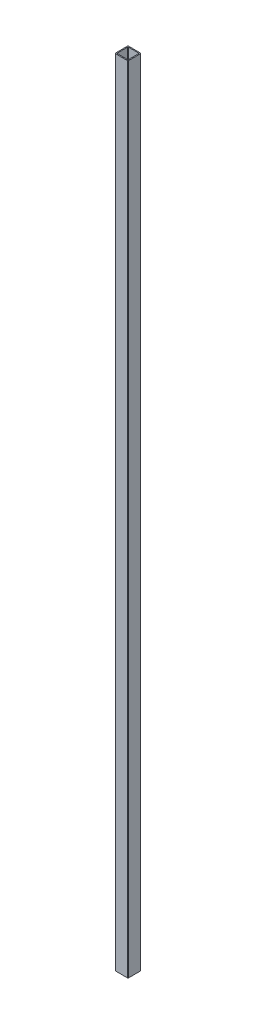
SolidWorks part; units mm, degrees
material "Hexcel AS4C (3000 Filaments)"
ref_plane "Front Plane" through (0, 0, 0) normal (0, 0, 1) x (1, 0, 0)
ref_plane "Top Plane" through (0, 0, 0) normal (0, 1, 0) x (1, 0, 0)
ref_plane "Right Plane" through (0, 0, 0) normal (1, 0, 0) x (0, 0, -1)
sketch "Sketch1" plane through (0, 0, 0) normal (0, 1, 0) x (1, 0, 0)
  line L1 (-9, -10) -> (9, -10)
  line L2 (-10, -9) -> (-10, 9)
  line L3 (-9, 10) -> (9, 10)
  line L4 (10, -9) -> (10, 9)
  line L5 (-10, -10) -> (10, 10) construction
  line L6 (-10, 10) -> (10, -10) construction
  line L7 (-7.5, -8.5) -> (7.5, -8.5)
  line L8 (-8.5, -7.5) -> (-8.5, 7.5)
  line L9 (-7.5, 8.5) -> (7.5, 8.5)
  line L10 (8.5, -7.5) -> (8.5, 7.5)
  line L11 (-8.5, -8.5) -> (8.5, 8.5) construction
  line L12 (-8.5, 8.5) -> (8.5, -8.5) construction
  arc A0 (-9, -10) -> (-10, -9) centre (-9, -9) cw
  arc A1 (9, 10) -> (10, 9) centre (9, 9) cw
  arc A2 (9, -10) -> (10, -9) centre (9, -9) ccw
  arc A3 (-10, 9) -> (-9, 10) centre (-9, 9) cw
  arc A4 (-7.5, -8.5) -> (-8.5, -7.5) centre (-7.5, -7.5) cw
  arc A5 (7.5, -8.5) -> (8.5, -7.5) centre (7.5, -7.5) ccw
  arc A6 (7.5, 8.5) -> (8.5, 7.5) centre (7.5, 7.5) cw
  arc A7 (-8.5, 7.5) -> (-7.5, 8.5) centre (-7.5, 7.5) cw
  point P0 (0, 0)
  point P18 (0, 0)
  dimension "D3" = 1
  dimension "D6" = 1
  dimension "D7" = 1
  dimension "D8" = 1
  dimension "D9" = 1
  dimension "D1" = 20
  dimension "D2" = 20
  dimension "D4" = 17
  dimension "D5" = 17
extrude "Boss-Extrude1" add sketch "Sketch1" along normal blind 1210
